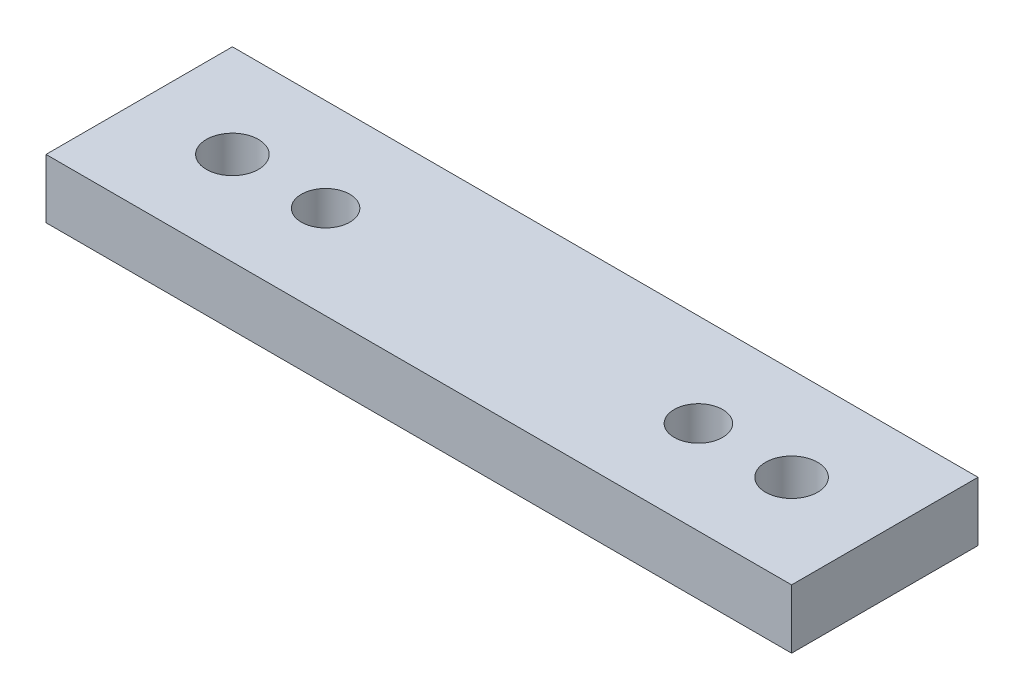
SolidWorks part; units mm, degrees
ref_plane "Front Plane" through (0, 0, 0) normal (0, 0, 1) x (1, 0, 0)
ref_plane "Top Plane" through (0, 0, 0) normal (0, 1, 0) x (1, 0, 0)
ref_plane "Right Plane" through (0, 0, 0) normal (1, 0, 0) x (0, 0, -1)
sketch "Sketch1" plane through (0, 0, 0) normal (0, 1, 0) x (1, 0, 0)
  line L0 (-30, 0) -> (30, 0) construction
  line L1 (-20, 0) -> (20, 0) construction
  line L2 (-40, 10) -> (40, 10)
  line L3 (-40, 10) -> (-40, -10)
  line L4 (-40, -10) -> (40, -10)
  line L5 (40, 10) -> (40, -10)
  line L6 (-40, 10) -> (40, -10) construction
  line L7 (-40, -10) -> (40, 10) construction
  circle A0 centre (-30, 0) radius 2.794
  circle A1 centre (30, 0) radius 2.794
  circle A2 centre (-20, 0) radius 2.6
  circle A3 centre (20, 0) radius 2.6
  point P4 (0, 0)
  point P7 (0, 0)
  point P15 (0, 0)
  dimension "D2" = 5.588
  dimension "D3" = 5.588
  dimension "D4" = 5.2
  dimension "D5" = 5.2
  dimension "D1" = 60
  dimension "D6" = 40
  dimension "D7" = 10
  dimension "D8" = 10
extrude "Boss-Extrude1" add sketch "Sketch1" along normal blind 3.175 and the other way blind 3.175
